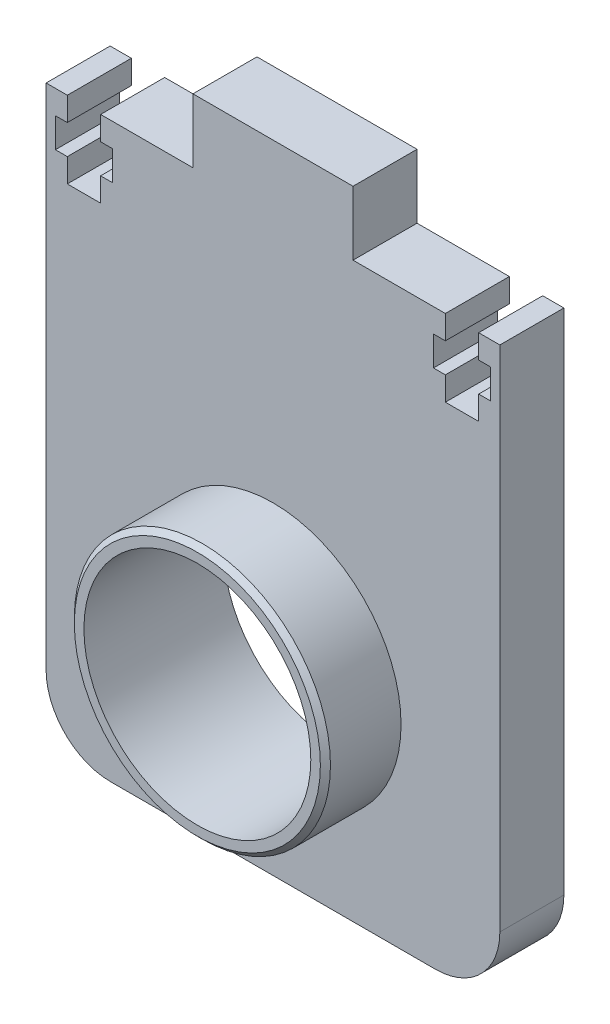
SolidWorks part; units mm, degrees
ref_plane "Front Plane" through (0, 0, 0) normal (0, 0, 1) x (1, 0, 0)
ref_plane "Top Plane" through (0, 0, 0) normal (0, 1, 0) x (1, 0, 0)
ref_plane "Right Plane" through (0, 0, 0) normal (1, 0, 0) x (0, 0, -1)
sketch "Sketch12" plane through (0, 0, 0) normal (0, 0, 1) x (1, 0, 0)
  line L0 (62.1258, 0) -> (62.1258, 126.33)
  line L1 (62.1258, 126.33) -> (152.1258, 126.33)
  line L2 (62.1258, 0) -> (152.1258, 0)
  line L3 (152.1258, 126.33) -> (152.1258, 0)
  line L4 (107.1258, 38.68) -> (107.1258, 126.33) construction
  circle A0 centre (107.1258, 38.68) radius 25.4
  circle A1 centre (107.1258, 38.68) radius 6.5
  point P8 (0, 0)
  dimension "D3" = 50.8
  dimension "D4" = 13
  dimension "D1" = 126.33
  dimension "D2" = 90
  dimension "D5" = 87.65
extrude "Boss-Extrude10" add sketch "Sketch12" along normal blind 12.7 separate body contours L1 L3 L2 L0
sketch "Sketch15" plane through (0, 0, 12.7) normal (0, 0, 1) x (1, 0, 0)
  line L0 (62.1258, 0) -> (152.1258, 0) construction
  circle A0 centre (107.1258, 38.6276) radius 25.4
  point P4 (107.1258, 0)
  dimension "D1" = 50.8
  dimension "D2" = 38.6276
extrude "Boss-Extrude11" add sketch "Sketch15" along normal blind 15
sketch "Sketch23" plane through (0, 0, 27.7) normal (0, 0, 1) x (1, 0, 0)
  circle A0 centre (107.1258, 38.6276) radius 22.5
  dimension "D1" = 45
extrude "Cut-Extrude7" cut sketch "Sketch23" against normal through all
fillet "Fillet2" radius 12.8 2 edges at (152.1258, 0, 6.35) (62.1258, 0, 6.35)
sketch "Sketch25" plane through (0, 0, 12.7) normal (0, 0, 1) x (1, 0, 0)
  line L0 (152.1258, 126.33) -> (152.1258, 113.63)
  line L1 (152.1258, 126.33) -> (152.1258, 12.8) construction
  line L2 (107.1258, 126.33) -> (107.1258, 98.7556)
  line L3 (62.1258, 12.8) -> (62.1258, 126.33) construction
  line L4 (62.1258, 113.63) -> (62.1258, 126.33)
  line L5 (123.0008, 113.63) -> (123.0008, 126.33)
  line L6 (62.1258, 126.33) -> (152.1258, 126.33) construction
  line L7 (123.0008, 126.33) -> (91.2508, 126.33)
  line L8 (91.2508, 126.33) -> (91.2508, 113.63)
  line L9 (91.2508, 113.63) -> (107.1258, 113.63)
  line L10 (107.1258, 113.63) -> (123.0008, 113.63)
  line L11 (152.1258, 113.63) -> (123.0008, 113.63)
  line L12 (123.0008, 126.33) -> (91.2508, 126.33)
  line L13 (91.2508, 113.63) -> (62.1258, 113.63)
  line M10 (152.1258, 12.8) -> (152.1258, 126.33)
  line M11 (152.1258, 126.33) -> (62.1258, 126.33)
  line M12 (62.1258, 126.33) -> (62.1258, 12.8)
  dimension "D1" = 12.7
  dimension "D2" = 31.75
extrude "Cut-Extrude9" cut sketch "Sketch25" against normal through all contours L13 L8 M11 M12 | L11 L5 M10 M11 region at (137.5633, 119.98, 12.7) region at (76.6883, 119.98, 12.7)
sketch "Sketch27" plane through (0, 0, 12.7) normal (0, 0, 1) x (1, 0, 0)
  line L0 (147.9178, 113.63) -> (147.9178, 108.931)
  line L1 (152.1258, 113.63) -> (123.0008, 113.63) construction
  line L2 (147.9178, 108.931) -> (150.2798, 108.931)
  line L3 (150.2798, 108.931) -> (150.2798, 103.089)
  line L4 (150.2798, 103.089) -> (147.9178, 103.089)
  line L5 (147.9178, 103.089) -> (147.9178, 98.39)
  line L6 (147.9178, 98.39) -> (141.3138, 98.39)
  line L7 (141.3138, 98.39) -> (141.3138, 103.089)
  line L8 (141.3138, 103.089) -> (138.9518, 103.089)
  line L9 (138.9518, 103.089) -> (138.9518, 108.931)
  line L10 (138.9518, 108.931) -> (141.3138, 108.931)
  line L11 (141.3138, 108.931) -> (141.3138, 113.63)
  line L12 (107.1258, 126.33) -> (107.1258, 67.6415) construction
  line L13 (91.2508, 126.33) -> (123.0008, 126.33) construction
  line L14 (72.9378, 103.089) -> (75.2998, 103.089)
  line L15 (75.2998, 103.089) -> (75.2998, 108.931)
  line L16 (75.2998, 108.931) -> (72.9378, 108.931)
  line L17 (72.9378, 108.931) -> (72.9378, 113.63)
  line L18 (66.3338, 113.63) -> (66.3338, 108.931)
  line L19 (66.3338, 108.931) -> (63.9718, 108.931)
  line L20 (63.9718, 108.931) -> (63.9718, 103.089)
  line L21 (63.9718, 103.089) -> (66.3338, 103.089)
  line L22 (66.3338, 103.089) -> (66.3338, 98.39)
  line L23 (66.3338, 98.39) -> (72.9378, 98.39)
  line L24 (72.9378, 98.39) -> (72.9378, 103.089)
  line L25 (147.9178, 113.63) -> (141.3138, 113.63)
  line L26 (72.9378, 113.63) -> (66.3338, 113.63)
  point P30 (144.6158, 113.63)
  point P31 (69.6358, 113.63)
  dimension "D1" = 6.604
  dimension "D2" = 11.328
  dimension "D3" = 15.24
  dimension "D4" = 5.842
  dimension "D5" = 74.98
ref_axis "Axis1" through (107.1258, 126.33, 12.7) along (0, -1, 0)
extrude "Cut-Extrude10" cut sketch "Sketch27" against normal through all
chamfer "Chamfer1" distance 1 angle 45 1 edges at (132.5258, 38.6276, 27.7)
